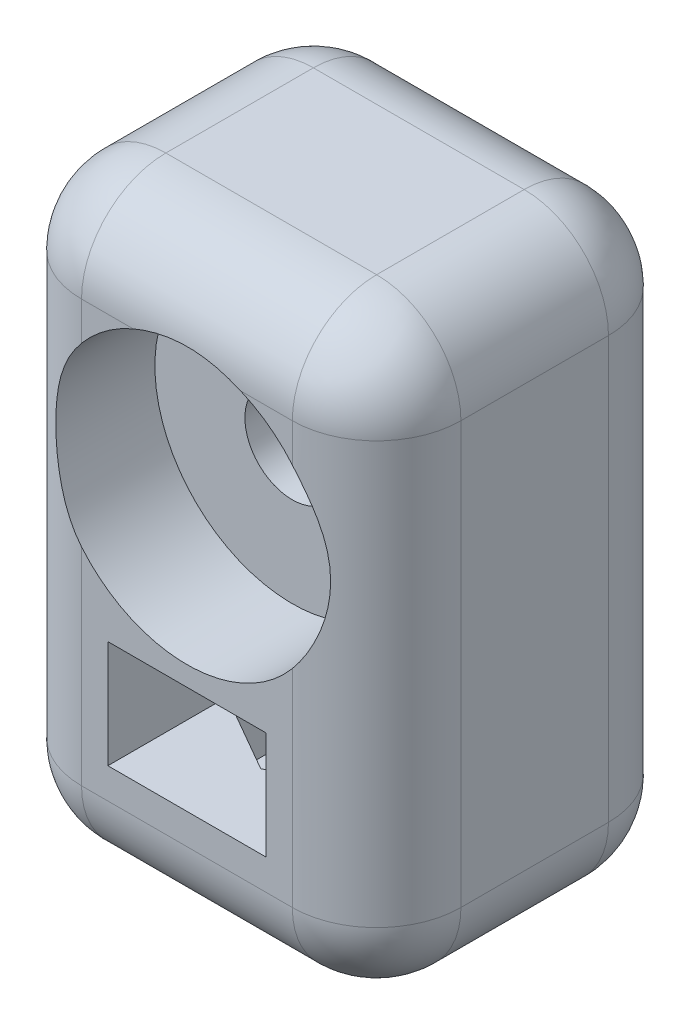
SolidWorks part; units mm, degrees
ref_plane "Front Plane" through (0, 0, 0) normal (0, 0, 1) x (1, 0, 0)
ref_plane "Top Plane" through (0, 0, 0) normal (0, 1, 0) x (1, 0, 0)
ref_plane "Right Plane" through (0, 0, 0) normal (1, 0, 0) x (0, 0, -1)
sketch "Sketch1" plane through (0, 0, 0) normal (0, 0, 1) x (1, 0, 0)
  line L0 (0, 0) -> (0, 24)
  line L1 (4, 28) -> (14, 28)
  line L2 (18, 24) -> (18, 0)
  line L7 (18, 0) -> (0, 0)
  line L8 (9, 28) -> (9, 0) construction
  line L9 (18, 18) -> (0, 18) construction
  circle A0 centre (9, 18) radius 6.52
  arc A2 (14, 28) -> (18, 24) centre (14, 24) cw
  arc A3 (0, 24) -> (4, 28) centre (4, 24) cw
  circle A4 centre (9, 18) radius 2.25
  dimension "D3" = 13.04
  dimension "D4" = 10
  dimension "D6" = 4.5
  dimension "D1" = 28
  dimension "D2" = 18
extrude "Boss-Extrude1" add sketch "Sketch1" along normal mid plane 15 contours A0 A4 | A3 L0 L7 L2 A2 L1 A0 region at (0.3329, 12, 0) region at (2.6644, 18, 0)
extrude "Cut-Extrude1" cut sketch "Sketch1<3>" along normal blind 5 from surface contours A0 A4 region at (2.6644, 18, 0) starting at face at (11.25, 18, -7.5)
sketch "Sketch1<3>" plane through (0, 0, 0) normal (0, 0, 1) x (1, 0, 0) same geometry as "Sketch1"
extrude "Cut-Extrude2" cut sketch "Sketch1<4>" against normal blind 5 from surface contours A0 A4 region at (2.6644, 18, 0) starting at face at (11.25, 18, 7.5)
sketch "Sketch1<4>" plane through (0, 0, 0) normal (0, 0, 1) x (1, 0, 0) same geometry as "Sketch1"
sketch "Sketch2" plane through (0, 0, 0) normal (0, -1, 0) x (1, 0, 0)
  line L0 (0, 7.5) -> (0, -7.5) construction
  line L3 (18, 7.5) -> (18, -7.5) construction
  line L5 (18, 0) -> (0, 0) construction
  line L9 (12.5, -7.5) -> (5.5, -7.5)
  line L12 (18, -7.5) -> (0, -7.5) construction
  line L14 (9.0059, 4) -> (5.5388, 2.0051)
  line L15 (5.5388, 2.0051) -> (5.533, -1.9949)
  line L16 (5.533, -1.9949) -> (8.9941, -4)
  line L17 (8.9941, -4) -> (12.4612, -2.0051)
  line L18 (12.4612, -2.0051) -> (12.467, 1.9949)
  line L19 (12.467, 1.9949) -> (9.0059, 4)
  circle A1 centre (9, 0) radius 2.1
  circle A2 centre (9, 0) radius 4 construction
  dimension "D2" = 4.2
  dimension "D4" = 8
fillet "Fillet1" radius 4 14 edges at (18, 12, 7.5) (16.8284, 26.8284, 7.5) (9, 28, 7.5) (1.1716, 26.8284, 7.5) (18, 12, -7.5) (16.8284, 26.8284, -7.5) (9, 28, -7.5) (1.1716, 26.8284, -7.5) (0, 12, 7.5) (0, 12, -7.5) (0, 0, 0) (9, 0, -7.5) (9, 0, 7.5) (18, 0, 0)
extrude "Cut-Extrude3" cut sketch "Sketch2" against normal blind 10 contours A1
sketch "Sketch3" plane through (0, 0, -7.5) normal (0, 0, -1) x (-1, 0, 0)
  line L0 (-9, 28) -> (-9, 0) construction
  line L1 (-14, 28) -> (-4, 28) construction
  line L2 (-4, 0) -> (-14, 0) construction
  line L3 (-12.75, 8) -> (0, 8) construction
  line L5 (0, 24) -> (0, 4) construction
  line L6 (-12.75, 5.45) -> (-5.25, 5.45)
  line L7 (-12.75, 10.55) -> (-5.25, 10.55)
  line L8 (-12.75, 10.55) -> (-12.75, 5.45)
  line L9 (-5.25, 10.55) -> (-5.25, 5.45)
  line L10 (-18, 10.55) -> (0, 10.55) construction
  line L11 (-18, 8) -> (0, 8) construction
  line L12 (-18, 5.45) -> (0, 5.45) construction
  line L13 (-5.25, 28) -> (-5.25, 0) construction
  line L14 (-12.75, 28) -> (-12.75, 0) construction
  dimension "D1" = 8
  dimension "D2" = 2.55
  dimension "D3" = 2.55
  dimension "D4" = 3.75
  dimension "D5" = 3.75
extrude "Cut-Extrude4" cut sketch "Sketch3" against normal through all contours L7 L9 L6 L8
extrude "Cut-Extrude5" cut sketch "Sketch2<7>" along normal blind 3 from surface contours L18 L19 L14 L15 L16 L17 A1 region at (10.6834, 0, 2.9059) starting at face at (9, 5.45, 0)
sketch "Sketch2<7>" plane through (0, 0, 0) normal (0, -1, 0) x (1, 0, 0) same geometry as "Sketch2"
equation "\"n\"=4"
